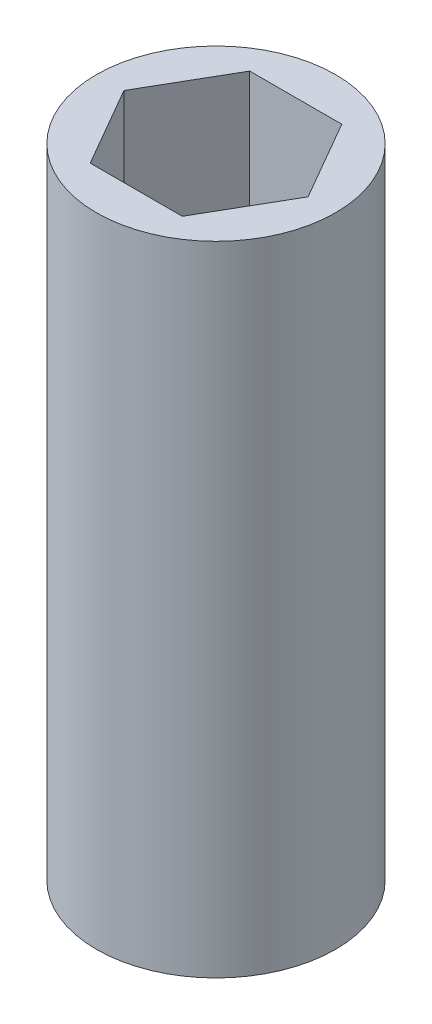
SolidWorks part; units mm, degrees
material "6061-T6 (SS)"
ref_plane "Front" through (0, 0, 0) normal (0, 0, 1) x (1, 0, 0)
ref_plane "Top" through (0, 0, 0) normal (0, 1, 0) x (1, 0, 0)
ref_plane "Right" through (0, 0, 0) normal (1, 0, 0) x (0, 0, -1)
sketch "Sketch1" plane through (0, 0, 0) normal (0, 1, 0) x (1, 0, 0)
  line L1 (3.6662, 6.35) -> (-3.6662, 6.35)
  line L2 (-3.6662, 6.35) -> (-7.3323, 0)
  line L3 (-7.3323, 0) -> (-3.6662, -6.35)
  line L4 (-3.6662, -6.35) -> (3.6662, -6.35)
  line L5 (3.6662, -6.35) -> (7.3323, 0)
  line L6 (7.3323, 0) -> (3.6662, 6.35)
  circle A0 centre (0, 0) radius 9.525
  circle A1 centre (0, 0) radius 6.35 construction
  point P3 (0, 0)
  dimension "D2" = 19.05
  dimension "D1" = 12.7
extrude "Boss-Extrude1" add sketch "Sketch1" along normal blind 50.8
